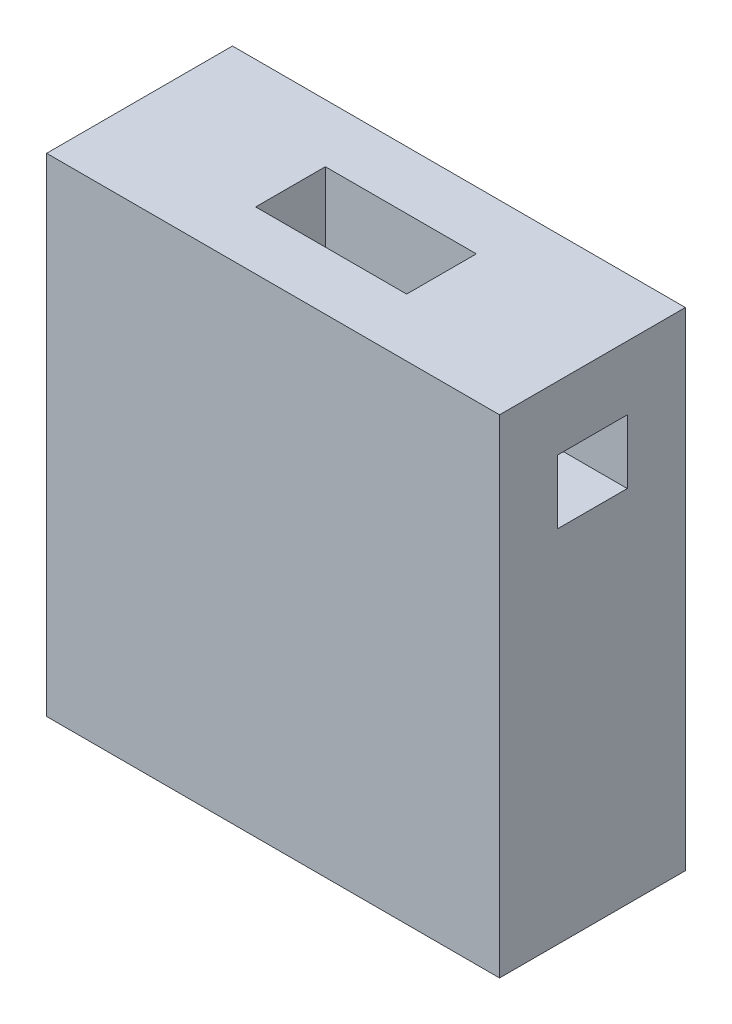
SolidWorks part; units mm, degrees
ref_plane "Plan de face" through (0, 0, 0) normal (0, 0, 1) x (1, 0, 0)
ref_plane "Plan de dessus" through (0, 0, 0) normal (0, 1, 0) x (1, 0, 0)
ref_plane "Plan de droite" through (0, 0, 0) normal (1, 0, 0) x (0, 0, -1)
sketch "Esquisse1" plane through (0, 0, 0) normal (0, 1, 0) x (1, 0, 0)
  line L1 (-19.5, 8) -> (19.5, 8)
  line L2 (-19.5, 8) -> (-19.5, -8)
  line L3 (-19.5, -8) -> (19.5, -8)
  line L4 (19.5, 8) -> (19.5, -8)
  line L5 (-19.5, 8) -> (19.5, -8) construction
  line L6 (-19.5, -8) -> (19.5, 8) construction
  point P0 (0, 0)
  dimension "D1" = 39
  dimension "D2" = 16
extrude "Boss.-Extru.1" add sketch "Esquisse1" along normal blind 42
sketch "Esquisse2" plane through (0, 42, 0) normal (0, 1, 0) x (1, 0, 0)
  line L1 (-6.5, -3) -> (6.5, -3)
  line L2 (-6.5, -3) -> (-6.5, 3)
  line L3 (-6.5, 3) -> (6.5, 3)
  line L4 (6.5, -3) -> (6.5, 3)
  line L5 (-6.5, -3) -> (6.5, 3) construction
  line L6 (-6.5, 3) -> (6.5, -3) construction
  point P0 (0, 0)
  dimension "D1" = 13
  dimension "D2" = 6
extrude "Enlèv. mat.-Extru.1" cut sketch "Esquisse2" against normal blind 11
sketch "Esquisse3" plane through (-6.5, 0, 0) normal (1, 0, 0) x (0, 0, -1)
  line L0 (3, 31) -> (3, 42) construction
  line L1 (-3, 31) -> (3, 31)
  line L2 (-3, 31) -> (-3, 36.5)
  line L3 (-3, 36.5) -> (3, 36.5)
  line L4 (3, 31) -> (3, 36.5)
extrude "Enlèv. mat.-Extru.2" cut sketch "Esquisse3" along normal through all
